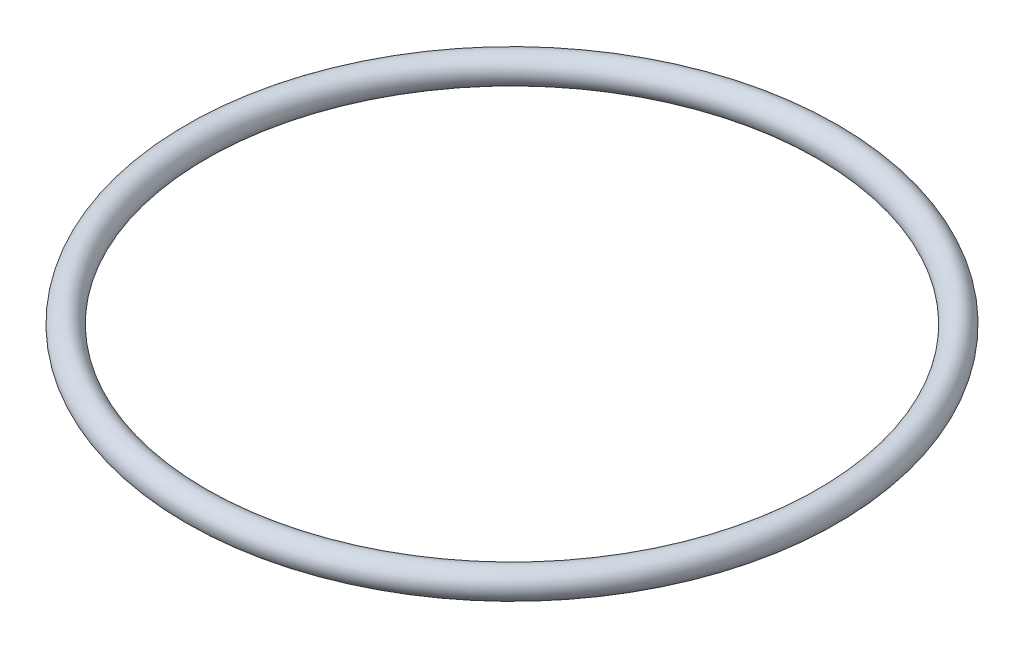
SolidWorks part; units mm, degrees
ref_plane "Alzado" through (0, 0, 0) normal (0, 0, 1) x (1, 0, 0)
ref_plane "Planta" through (0, 0, 0) normal (0, 1, 0) x (1, 0, 0)
ref_plane "Vista lateral" through (0, 0, 0) normal (1, 0, 0) x (0, 0, -1)
sketch "Croquis2" plane through (0, 0, 0) normal (1, 0, 0) x (0, 0, -1)
  line L0 (-29.72, 5.1199) -> (-29.72, -4.0367) construction
  circle A0 centre (0, 0) radius 1.31
  dimension "D1" = 2.62
  dimension "D2" = 29.72
revolve "Revolución1" add sketch "Croquis2" angle 360 about L0
sketch "Croquis3" plane through (0, 0, 0) normal (1, 0, 0) x (0, 0, -1)
  line L0 (-29.72, 17.7809) -> (-29.72, -16.924) construction
  dimension "D1" = 29.72
ref_plane "Plane1" through (0, 0, 29.72) normal (0, 0, 1) x (1, 0, 0)
ref_axis "Axis1" through (0, -1.441, 29.72) along (0, 1, 0)
ref_plane "Plane2" through (0, 1.31, 0) normal (0, 1, 0) x (1, 0, 0)
